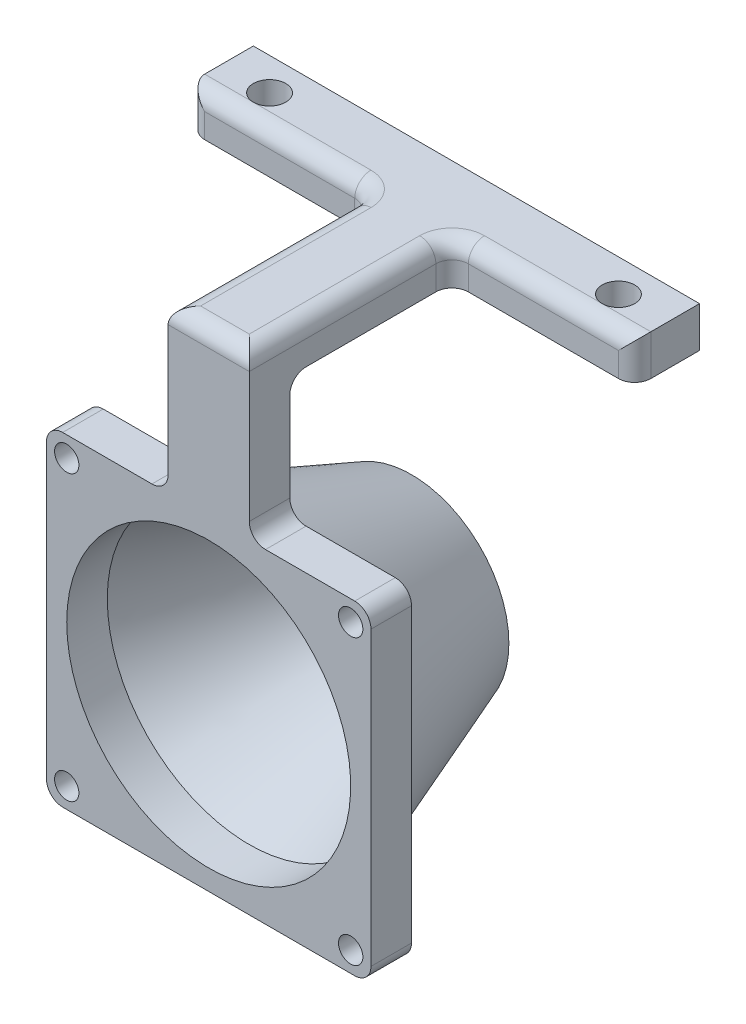
SolidWorks part; units mm, degrees
ref_plane "Plan de face" through (0, 0, 0) normal (0, 0, 1) x (1, 0, 0)
ref_plane "Plan de dessus" through (0, 0, 0) normal (0, 1, 0) x (1, 0, 0)
ref_plane "Plan de droite" through (0, 0, 0) normal (1, 0, 0) x (0, 0, -1)
sketch "Esquisse1" plane through (0, 0, 0) normal (0, 1, 0) x (1, 0, 0)
  circle A0 centre (-21.5, -15.7391) radius 2
  circle A1 centre (21.5, -15.7391) radius 2
  circle A2 centre (0, 21.5) radius 2
  dimension "D1" = 4
  dimension "D2" = 4
  dimension "D5" = 4
  dimension "D3" = 43
  dimension "D4" = 21.5
  dimension "D6" = 43
  dimension "D7" = 43
  dimension "D8" = 21.5
sketch "Esquisse2" plane through (0, 0, 0) normal (0, 1, 0) x (1, 0, 0)
  line L0 (5, -19.7391) -> (27.5, -19.7391)
  line L1 (-27.5, -11.7391) -> (27.5, -11.7391)
  line L2 (-27.5, -11.7391) -> (-27.5, -19.7391)
  line L3 (-27.5, -19.7391) -> (-5, -19.7391)
  line L4 (27.5, -11.7391) -> (27.5, -19.7391)
  line L6 (-5, -19.7391) -> (-5, -39.7391)
  line L7 (-5, -39.7391) -> (5, -39.7391)
  line L8 (5, -19.7391) -> (5, -39.7391)
  circle A0 centre (-21.5, -15.7391) radius 2 construction
  circle A1 centre (-21.5, -15.7391) radius 2
  circle A2 centre (21.5, -15.7391) radius 2 construction
  circle A3 centre (21.5, -15.7391) radius 2
  dimension "D1" = 8
  dimension "D2" = 55
  dimension "D3" = 27.5
  dimension "D4" = 4
  dimension "D5" = 10
  dimension "D6" = 5
  dimension "D7" = 20
extrude "Boss.-Extru.1" add sketch "Esquisse2" along normal blind 5
sketch "Esquisse3" plane through (0, 0, 39.7391) normal (0, 0, 1) x (1, 0, 0)
  line L0 (5, 5) -> (5, 0) construction
  line L1 (-5, 5) -> (5, 5)
  line L2 (-5, 5) -> (-5, -15)
  line L3 (5, -15) -> (20, -15)
  line L4 (5, 5) -> (5, -15)
  line L6 (-20, -15) -> (-5, -15)
  line L7 (-20, -15) -> (-20, -55)
  line L8 (-20, -55) -> (20, -55)
  line L9 (20, -15) -> (20, -55)
  circle A0 centre (-17.5, -17.5) radius 1.5
  circle A1 centre (17.5, -17.5) radius 1.5
  circle A2 centre (17.5, -52.5) radius 1.5
  circle A3 centre (-17.5, -52.5) radius 1.5
  dimension "D5" = 2.5
  dimension "D7" = 3
  dimension "D8" = 3
  dimension "D9" = 3
  dimension "D10" = 3
  dimension "D1" = 20
  dimension "D2" = 40
  dimension "D3" = 40
  dimension "D4" = 20
  dimension "D6" = 2.5
  dimension "D11" = 2.5
  dimension "D12" = 2.5
  dimension "D13" = 2.5
  dimension "D14" = 2.5
  dimension "D15" = 2.5
  dimension "D16" = 2.5
extrude "Boss.-Extru.2" add sketch "Esquisse3" along normal blind 5
ref_plane "Plan1" through (0, 0, 19.7391) normal (0, 0, -1) x (-1, 0, 0)
sketch "Esquisse5" plane through (0, 0, 39.7391) normal (0, 0, -1) x (-1, 0, 0)
  line L0 (-20, -15) -> (-5, -15) construction
  line L1 (-20, -55) -> (-20, -15) construction
  circle A0 centre (0, -35) radius 17.5
  dimension "D1" = 35
  dimension "D2" = 20
  dimension "D3" = 20
extrude "Enlèv. mat.-Extru.1" cut sketch "Esquisse5" against normal through all
sketch "Esquisse7" plane through (0, 0, 39.7391) normal (0, 0, -1) x (-1, 0, 0)
  circle A2 centre (0, -35) radius 19.5
  circle A3 centre (0, -35) radius 19.5
  dimension "D1" = 2
sketch "Esquisse8" plane through (0, 0, 19.7391) normal (0, 0, -1) x (-1, 0, 0)
  circle A1 centre (0, -35) radius 12
loft "Lissage3" add section "Esquisse7" section "Esquisse8" connector at (12.8588, -20.3405, 39.7391) connector at (8.1539, -26.1958, 19.7391)
sketch "Esquisse9" plane through (0, 0, 19.7391) normal (0, 0, -1) x (-1, 0, 0)
  circle A2 centre (0, -35) radius 10
  circle A3 centre (0, -35) radius 10
  dimension "D1" = 2
sketch "Esquisse10" plane through (0, 0, 39.7391) normal (0, 0, 1) x (1, 0, 0)
  circle A1 centre (0, -35) radius 17.5
  circle A2 centre (0, -35) radius 17.5
  dimension "D1" = 0
loft "Enlèvement de matière-Lissage1" cut profiles "Esquisse10", "Esquisse9" connector at (16.0034, -27.919, 39.7391) connector at (7.155, -28.0138, 19.7391)
fillet "Congé2" radius 2 16 edges at (-20, -15, 42.2391) (-20, -55, 42.2391) (20, -55, 42.2391) (20, -15, 42.2391) (-5, 5, 32.2391) (5, 5, 32.2391) (5, -15, 42.2391) (-5, -15, 42.2391) (-16.25, 5, 19.7391) (16.25, 5, 19.7391) (0, 5, 44.7391) (27.5, 2.5, 19.7391) (-27.5, 2.5, 19.7391) (-5, 2.5, 19.7391) (5, 2.5, 19.7391)
